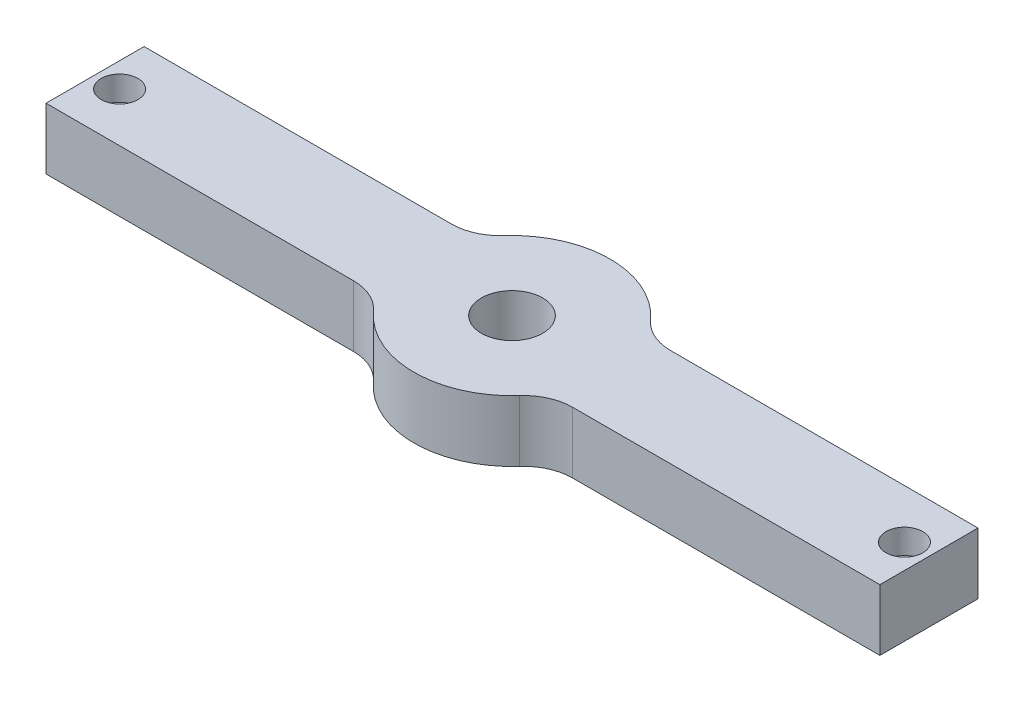
SolidWorks part; units mm, degrees
material "6061-T6 (SS)"
ref_plane "Front Plane" through (0, 0, 0) normal (0, 0, 1) x (1, 0, 0)
ref_plane "Top Plane" through (0, 0, 0) normal (0, 1, 0) x (1, 0, 0)
ref_plane "Right Plane" through (0, 0, 0) normal (1, 0, 0) x (0, 0, -1)
sketch "Sketch2" plane through (0, 0, 0) normal (0, 1, 0) x (1, 0, 0)
  line L0 (-21.997, 0) -> (0, 0) construction
  line L1 (-107.95, -25.4) -> (-21.997, -25.4)
  line L2 (-107.95, -25.4) -> (-107.95, 0)
  line L3 (-107.95, 0) -> (-21.997, 0)
  line L4 (-21.997, -25.4) -> (-21.997, 0)
  line L5 (21.997, -25.4) -> (107.95, -25.4)
  line L6 (21.997, -25.4) -> (21.997, 0)
  line L7 (21.997, 0) -> (107.95, 0)
  line L8 (107.95, -25.4) -> (107.95, 0)
  line L9 (0, 0) -> (21.997, 0) construction
  circle A0 centre (0, -12.7) radius 7.9375
  circle A1 centre (0, -12.7) radius 25.4
  point P13 (107.95, -12.7)
  dimension "D3" = 215.9
  dimension "D4" = 15.875
  dimension "D5" = 50.8
  dimension "D1" = 25.4
  dimension "D2" = 25.4
extrude "Boss-Extrude1" add sketch "Sketch2" along normal blind 15.875 contours A1 L3 L2 L1 | L4 A1 | L6 A1 L4 A0 | L6 A1 | A1 L5 L8 L7 region at (-66.1179, 0, 12.7) region at (-23.3664, 0, 12.7) region at (-21.325, 0, 12.7) region at (66.1179, 0, 12.7) region at (23.3664, 0, 12.7)
fillet "Fillet1" radius 12.7 4 edges at (21.997, 7.9375, 0) (21.997, 7.9375, 25.4) (-21.997, 7.9375, 25.4) (-21.997, 7.9375, 0)
sketch "Sketch3" plane through (0, 0, 0) normal (0, -1, 0) x (1, 0, 0)
  circle A0 centre (0, 12.7) radius 22.225
  dimension "D1" = 44.45
extrude "Cut-Extrude1" cut sketch "Sketch3" against normal blind 3.175
sketch "Sketch4" plane through (0, 15.875, 0) normal (0, 1, 0) x (1, 0, 0)
  line L0 (-107.95, -25.4) -> (-107.95, 0) construction
  line L1 (107.95, -25.4) -> (107.95, 0) construction
  circle A0 centre (-101.6, -12.7) radius 4.7625
  circle A1 centre (101.6, -12.7) radius 4.7625
  point P4 (-107.95, -12.7)
  point P5 (107.95, -12.7)
  dimension "D1" = 9.525
  dimension "D2" = 9.525
  dimension "D3" = 6.35
  dimension "D4" = 6.35
extrude "Cut-Extrude2" cut sketch "Sketch4" against normal blind 6.35
sketch "Sketch5" plane through (0, 9.525, 0) normal (0, 1, 0) x (1, 0, 0)
  circle A0 centre (-101.6, -12.7) radius 3.175
  circle A1 centre (101.6, -12.7) radius 3.175
  dimension "D1" = 6.35
  dimension "D2" = 6.35
extrude "Cut-Extrude3" cut sketch "Sketch5" against normal through all
